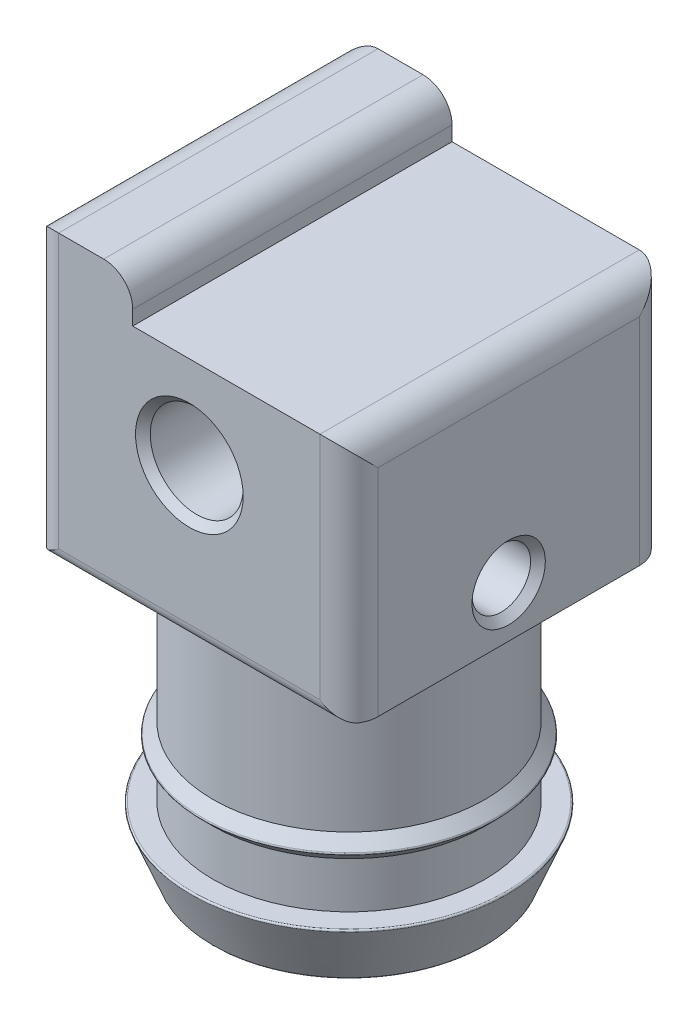
SolidWorks part; units mm, degrees
ref_plane "Front Plane" through (0, 0, 0) normal (0, 0, 1) x (1, 0, 0)
ref_plane "Top Plane" through (0, 0, 0) normal (0, 1, 0) x (1, 0, 0)
ref_plane "Right Plane" through (0, 0, 0) normal (1, 0, 0) x (0, 0, -1)
sketch "Sketch1" plane through (0, 0, 0) normal (0, 0, 1) x (1, 0, 0)
  line L3 (0, 0) -> (0, -10.5) construction
  line L4 (-11, 0) -> (-6.35, 0)
  line L5 (-11, 0) -> (-11, -10.5)
  line L6 (-11, -10.5) -> (11, -10.5)
  line L7 (11, 0) -> (11, -10.5)
  line L8 (6.35, 0) -> (11, 0)
  line L9 (11, 0) -> (11, 6.35)
  line L10 (11, 6.35) -> (-11, 6.35)
  line L11 (-11, 6.35) -> (-11, 0)
  circle A0 centre (0, 0) radius 3.2
  arc A1 (6.35, 0) -> (-6.35, 0) centre (0, 0) ccw
  dimension "D1" = 6.4
  dimension "D2" = 12.7
  dimension "D4" = 22
  dimension "D5" = 10.5
extrude "Boss-Extrude1" add sketch "Sketch1" along normal mid plane 22
sketch3d "3DSketch1" plane through (0, 0, 0) normal (0, 0, 1) x (1, 0, 0)
  dimension "D1" = 12.7
sketch "Sketch2" plane through (0, 0, 0) normal (0, 0, 1) x (1, 0, 0)
  line L0 (0, 9.544) -> (0, -9.544) construction
  line L1 (0, -10) -> (9.365, -10)
  line L4 (0, -29.5) -> (9.365, -29.5)
  line L10 (0, -29.5) -> (0, -10)
  line L11 (9.365, -29.5) -> (10.9525, -25.5312)
  line L12 (10.9525, -25.5312) -> (9.365, -25.5312)
  line L13 (9.365, -25.5312) -> (9.365, -22.3562)
  line L14 (9.365, -22.3562) -> (10.1587, -21.5625)
  line L15 (10.1587, -21.5625) -> (9.365, -20.7688)
  line L16 (10.1587, -21.5625) -> (9.365, -21.5625) construction
  line L17 (9.365, -20.7688) -> (9.365, -10)
  dimension "D1" = 18.73
  dimension "D2" = 19.5
  dimension "D3" = 1.5875
  dimension "D4" = 3.9688
  dimension "D5" = 0.7937
  dimension "D6" = 7.9375
  dimension "D7" = 10
revolve "Revolve1" add sketch "Sketch2" angle 360 about L0
sketch "Sketch3" plane through (0, -29.5, 0) normal (0, -1, 0) x (1, 0, 0)
  circle A0 centre (0, 0) radius 2.3813
  dimension "D1" = 4.7625
extrude "Cut-Extrude1" cut sketch "Sketch3" against normal blind 25 contours A0
hole_wizard "#10-32 Tapped Hole1" positions "Sketch4" profile "Sketch5" tap size "#10-32" standard "ANSI Inch"
sketch "Sketch4" plane through (11, 0, 0) normal (1, 0, 0) x (0, 0, -1)
  point P0 (0, -7)
  dimension "D1" = 7
sketch "Sketch5" plane through (11, -7, 0) normal (0, 1, 0) x (0, 0, -1)
  line L0 (0, 0) -> (0, 8.6188)
  line L1 (0, 8.6188) -> (2.0193, 8.6188)
  line L2 (2.0193, 8.6188) -> (2.0193, 0)
  line L5 (2.0193, 0) -> (0, 0)
  line L11 (0, -6.35) -> (0, 107.95) construction
  dimension "Thru Tap Drill Dia." = 4.0386
  dimension "Thru Tap Drill Depth" = 8.6188
cosmetic thread "Hole Thread1" parameters "D2"=4.826
fillet "Fillet3" radius 0.0992 6 edges at (-10.9525, -25.5312, 0) (-10.1587, -21.5625, 0) (2.3813, -29.5, 0) (2.3813, -4.5, 0) (2.3577, -8.9915, -0.3339) (-9.365, -29.5, 0)
chamfer "Chamfer1" distance 0.508 angle 45 3 edges at (11, -7, -2.0193) (3.2, 0, 11) (3.2, 0, -11)
fillet "Fillet6" radius 1 2 edges at (0, -10.5, -11) (0, -10.5, 11)
sketch "Sketch6" plane through (0, 6.35, 0) normal (0, 1, 0) x (1, 0, 0)
  line L0 (0, 0) -> (0, -50000) construction
  line L1 (-3.9, -11) -> (-3.9, 11)
  line L2 (11, -11) -> (-11, -11) construction
  line L3 (11, 11) -> (-11, 11) construction
  line L4 (-3.9, -11) -> (-11, -11)
  line L5 (-11, -11) -> (-11, 11)
  line L6 (-11, 11) -> (-3.9, 11)
  line L7 (11, -11) -> (11, 11)
  line L8 (3.9, -11) -> (11, -11)
  line L9 (3.9, -11) -> (3.9, 11)
  line L10 (11, 11) -> (3.9, 11)
  dimension "D1" = 3.9
extrude "Boss-Extrude2" add sketch "Sketch6" along normal blind 3 contours L6 L1 L4 L5
fillet "Fillet7" radius 2 2 edges at (-3.9, 9.35, 0) (11, 6.35, 0)
fillet "Fillet8" radius 2 5 edges at (-11, -0.075, -11) (-11, -0.075, 11) (11, -2.575, -11) (11, -2.575, 11) (-11, 9.35, 0)
